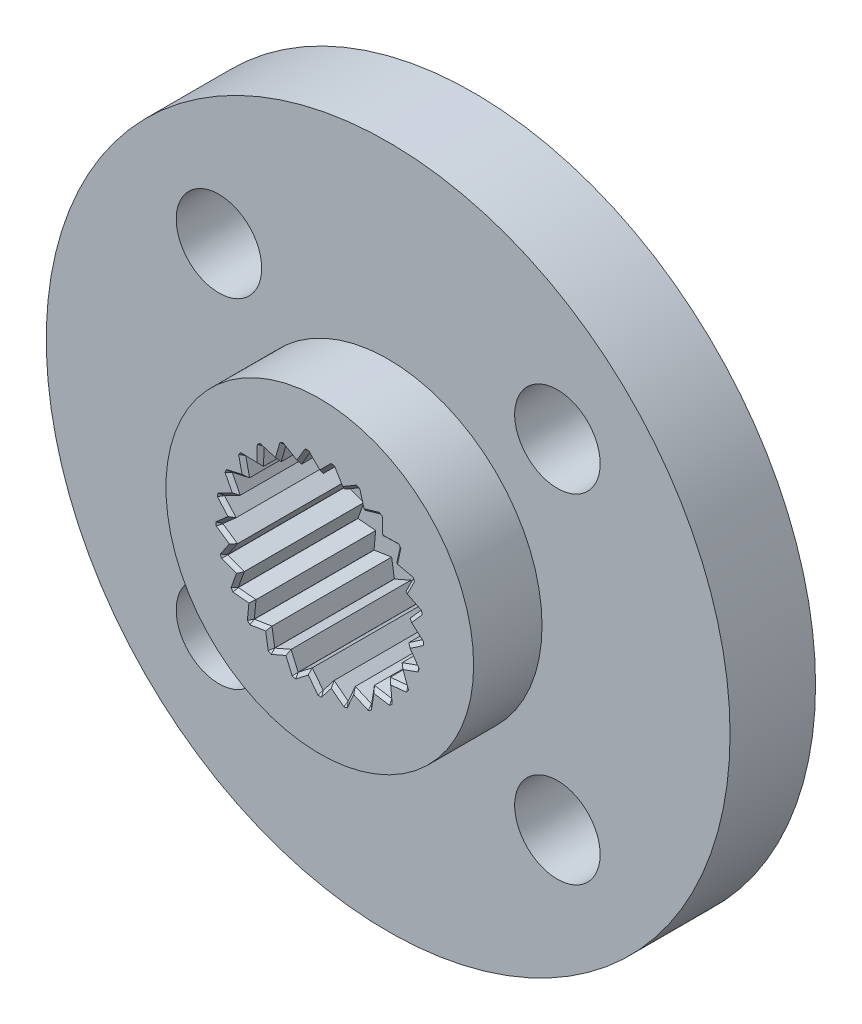
SolidWorks part; units mm, degrees
material "1060-H12"
ref_plane "前视基准面" through (0, 0, 0) normal (0, 0, 1) x (1, 0, 0)
ref_plane "上视基准面" through (0, 0, 0) normal (0, 1, 0) x (1, 0, 0)
ref_plane "右视基准面" through (0, 0, 0) normal (1, 0, 0) x (0, 0, -1)
sketch "草图1" plane through (0, 0, 0) normal (0, 0, 1) x (1, 0, 0)
  line L0 (-4.9497, 4.9497) -> (4.9497, 4.9497) construction
  line L1 (4.9497, 4.9497) -> (4.9497, -4.9497) construction
  circle A0 centre (0, 0) radius 10
  circle A1 centre (-4.9497, 4.9497) radius 1.25
  circle A2 centre (4.9497, 4.9497) radius 1.25
  circle A3 centre (4.9497, -4.9497) radius 1.25
  circle A4 centre (-4.9497, -4.9497) radius 1.25
  circle A5 centre (0, 0) radius 7 construction
  circle A6 centre (0, 0) radius 1.5
  dimension "D1" = 20
  dimension "D2" = 2.5
  dimension "D3" = 3
  dimension "D4" = 14
extrude "凸台-拉伸1" add sketch "草图1" along normal blind 2.5
cosmetic thread "装饰螺纹线1" parameters "D2"=3
cosmetic thread "装饰螺纹线2" parameters "D2"=3
cosmetic thread "装饰螺纹线3" parameters "D2"=3
cosmetic thread "装饰螺纹线4" parameters "D2"=3
sketch "草图2" plane through (0, 0, 2.5) normal (0, 0, 1) x (1, 0, 0)
  circle A0 centre (0, 0) radius 4.5
  circle A1 centre (0, 0) radius 1.5
  dimension "D1" = 9
extrude "凸台-拉伸2" add sketch "草图2" along normal blind 2
sketch "草图3" plane through (0, 0, 4.5) normal (0, 0, 1) x (1, 0, 0)
  line L0 (0, 2.55) -> (-0.3665, 2.9165)
  line L1 (-0.3665, 2.9165) -> (0.3665, 2.9165)
  line L2 (0.3665, 2.9165) -> (0, 2.55)
  line L75 (1.0803, 2.7337) -> (0.6342, 2.4699)
  line L76 (0.6342, 2.4699) -> (0.3703, 2.916)
  line L77 (0.3703, 2.916) -> (1.0803, 2.7337)
  line L78 (1.7262, 2.3792) -> (1.2285, 2.2346)
  line L79 (1.2285, 2.2346) -> (1.0839, 2.7323)
  line L80 (1.0839, 2.7323) -> (1.7262, 2.3792)
  line L81 (2.2636, 1.8752) -> (1.7456, 1.8589)
  line L82 (1.7456, 1.8589) -> (1.7293, 2.3769)
  line L83 (1.7293, 2.3769) -> (2.2636, 1.8752)
  line L84 (2.6589, 1.2533) -> (2.153, 1.3664)
  line L85 (2.153, 1.3664) -> (2.2661, 1.8722)
  line L86 (2.2661, 1.8722) -> (2.6589, 1.2533)
  line L87 (2.887, 0.5527) -> (2.4252, 0.788)
  line L88 (2.4252, 0.788) -> (2.6605, 1.2498)
  line L89 (2.6605, 1.2498) -> (2.887, 0.5527)
  line L90 (2.9338, -0.1826) -> (2.545, 0.1601)
  line L91 (2.545, 0.1601) -> (2.8877, 0.5489)
  line L92 (2.8877, 0.5489) -> (2.9338, -0.1826)
  line L93 (2.7962, -0.9065) -> (2.5048, -0.4778)
  line L94 (2.5048, -0.4778) -> (2.9335, -0.1865)
  line L95 (2.9335, -0.1865) -> (2.7962, -0.9065)
  line L96 (2.4829, -1.5734) -> (2.3073, -1.0857)
  line L97 (2.3073, -1.0857) -> (2.795, -0.9102)
  line L98 (2.795, -0.9102) -> (2.4829, -1.5734)
  line L99 (2.0136, -2.1414) -> (1.9648, -1.6254)
  line L100 (1.9648, -1.6254) -> (2.4808, -1.5767)
  line L101 (2.4808, -1.5767) -> (2.0136, -2.1414)
  line L102 (1.4178, -2.5749) -> (1.4989, -2.063)
  line L103 (1.4989, -2.063) -> (2.0108, -2.1441)
  line L104 (2.0108, -2.1441) -> (1.4178, -2.5749)
  line L105 (0.7329, -2.8466) -> (0.9387, -2.3709)
  line L106 (0.9387, -2.3709) -> (1.4144, -2.5768)
  line L107 (1.4144, -2.5768) -> (0.7329, -2.8466)
  line L108 (0.0019, -2.9394) -> (0.3196, -2.5299)
  line L109 (0.3196, -2.5299) -> (0.7291, -2.8476)
  line L110 (0.7291, -2.8476) -> (0.0019, -2.9394)
  line L111 (-0.7291, -2.8476) -> (-0.3196, -2.5299)
  line L112 (-0.3196, -2.5299) -> (-0.0019, -2.9394)
  line L113 (-0.0019, -2.9394) -> (-0.7291, -2.8476)
  line L114 (-1.4144, -2.5768) -> (-0.9387, -2.3709)
  line L115 (-0.9387, -2.3709) -> (-0.7329, -2.8466)
  line L116 (-0.7329, -2.8466) -> (-1.4144, -2.5768)
  line L117 (-2.0108, -2.1441) -> (-1.4989, -2.063)
  line L118 (-1.4989, -2.063) -> (-1.4178, -2.5749)
  line L119 (-1.4178, -2.5749) -> (-2.0108, -2.1441)
  line L120 (-2.4808, -1.5767) -> (-1.9648, -1.6254)
  line L121 (-1.9648, -1.6254) -> (-2.0136, -2.1414)
  line L122 (-2.0136, -2.1414) -> (-2.4808, -1.5767)
  line L123 (-2.795, -0.9102) -> (-2.3073, -1.0857)
  line L124 (-2.3073, -1.0857) -> (-2.4829, -1.5734)
  line L125 (-2.4829, -1.5734) -> (-2.795, -0.9102)
  line L126 (-2.9335, -0.1865) -> (-2.5048, -0.4778)
  line L127 (-2.5048, -0.4778) -> (-2.7962, -0.9065)
  line L128 (-2.7962, -0.9065) -> (-2.9335, -0.1865)
  line L129 (-2.8877, 0.5489) -> (-2.545, 0.1601)
  line L130 (-2.545, 0.1601) -> (-2.9338, -0.1826)
  line L131 (-2.9338, -0.1826) -> (-2.8877, 0.5489)
  line L132 (-2.6605, 1.2498) -> (-2.4252, 0.788)
  line L133 (-2.4252, 0.788) -> (-2.887, 0.5527)
  line L134 (-2.887, 0.5527) -> (-2.6605, 1.2498)
  line L135 (-2.2661, 1.8722) -> (-2.153, 1.3664)
  line L136 (-2.153, 1.3664) -> (-2.6589, 1.2533)
  line L137 (-2.6589, 1.2533) -> (-2.2661, 1.8722)
  line L138 (-1.7293, 2.3769) -> (-1.7456, 1.8589)
  line L139 (-1.7456, 1.8589) -> (-2.2636, 1.8752)
  line L140 (-2.2636, 1.8752) -> (-1.7293, 2.3769)
  line L141 (-1.0839, 2.7323) -> (-1.2285, 2.2346)
  line L142 (-1.2285, 2.2346) -> (-1.7262, 2.3792)
  line L143 (-1.7262, 2.3792) -> (-1.0839, 2.7323)
  line L144 (-0.3703, 2.916) -> (-0.6342, 2.4699)
  line L145 (-0.6342, 2.4699) -> (-1.0803, 2.7337)
  line L146 (-1.0803, 2.7337) -> (-0.3703, 2.916)
  circle A0 centre (0, 0) radius 2.55 construction
  circle A1 centre (0, 0) radius 2.9394
  point P154 (0, 0)
  dimension "D1" = 5.1
  dimension "D2" = 90
  dimension "D3" = 25
extrude "切除-拉伸1" cut sketch "草图3" against normal blind 3.6 contours L91 A1 L87 L88 L84 L85 L81 L82 L78 L79 L75 L76 L2 L0 L144 L145 L141 L142 L138 L139 L135 L136 L132 L133 L129 L130 L126 L127 L123 L124 L120 L121 L117 L118 L114
chamfer "倒角1" distance 0.1 angle 45 75 edges at (2.8874, 0.5508, 4.5) (2.6561, 0.6703, 4.5) (2.5428, 1.0189, 4.5) (2.6597, 1.2515, 4.5) (2.4059, 1.3098, 4.5) (2.2096, 1.6193, 4.5) (2.2649, 1.8737, 4.5) (2.0046, 1.867, 4.5) (1.7375, 2.1179, 4.5) (1.7278, 2.3781, 4.5) (1.4773, 2.3069, 4.5) (1.1562, 2.4834, 4.5) (1.0821, 2.733, 4.5) (0.8572, 2.6018, 4.5) (0.5022, 2.6929, 4.5) (0.3684, 2.9163, 4.5) (0.1832, 2.7332, 4.5) (-0.1832, 2.7332, 4.5) (-0.3684, 2.9163, 4.5) (-0.5022, 2.6929, 4.5) (-0.8572, 2.6018, 4.5) (-1.0821, 2.733, 4.5) (-1.1562, 2.4834, 4.5) (-1.4773, 2.3069, 4.5) (-1.7278, 2.3781, 4.5) (-1.7375, 2.1179, 4.5) (-2.0046, 1.867, 4.5) (-2.2649, 1.8737, 4.5) (-2.2096, 1.6193, 4.5) (-2.4059, 1.3098, 4.5) (-2.6597, 1.2515, 4.5) (-2.5428, 1.0189, 4.5) (-2.6561, 0.6703, 4.5) (-2.8874, 0.5508, 4.5) (-2.7163, 0.3545, 4.5) (-2.7394, -0.0113, 4.5) (-2.9336, -0.1846, 4.5) (-2.7192, -0.3322, 4.5) (-2.6505, -0.6922, 4.5) (-2.7956, -0.9083, 4.5) (-2.5511, -0.998, 4.5) (-2.3951, -1.3296, 4.5) (-2.4818, -1.575, 4.5) (-2.2228, -1.601, 4.5) (-1.9892, -1.8834, 4.5) (-2.0122, -2.1428, 4.5) (-1.7548, -2.1035, 4.5) (-1.4583, -2.319, 4.5) (-1.4161, -2.5758, 4.5) (-1.1766, -2.4739, 4.5) (-0.8358, -2.6088, 4.5) (-0.731, -2.8471, 4.5) (-0.5244, -2.6887, 4.5) (-0.1608, -2.7347, 4.5) (0, -2.9394, 4.5) (0.1608, -2.7347, 4.5) (0.5244, -2.6887, 4.5) (0.731, -2.8471, 4.5) (0.8358, -2.6088, 4.5) (1.1766, -2.4739, 4.5) (1.4161, -2.5758, 4.5) (1.4583, -2.319, 4.5) (1.7548, -2.1035, 4.5) (2.0122, -2.1428, 4.5) (1.9892, -1.8834, 4.5) (2.2228, -1.601, 4.5) (2.4818, -1.575, 4.5) (2.3951, -1.3296, 4.5) (2.5511, -0.998, 4.5) (2.7956, -0.9083, 4.5) (2.6505, -0.6922, 4.5) (2.7192, -0.3322, 4.5) (2.9336, -0.1846, 4.5) (2.7394, -0.0113, 4.5) (2.7163, 0.3545, 4.5)
